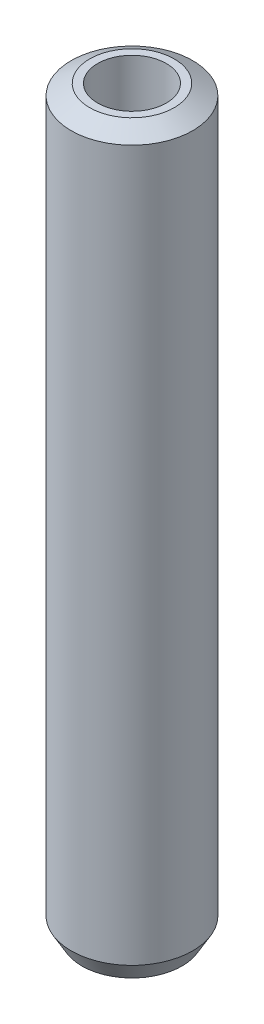
SolidWorks part; units mm, degrees
ref_plane "Front Plane" through (0, 0, 0) normal (0, 0, 1) x (1, 0, 0)
ref_plane "Top Plane" through (0, 0, 0) normal (0, 1, 0) x (1, 0, 0)
ref_plane "Right Plane" through (0, 0, 0) normal (1, 0, 0) x (0, 0, -1)
sketch "Sketch1" plane through (0, 0, 0) normal (0, 1, 0) x (1, 0, 0)
  circle A0 centre (0, 0) radius 7.5
  dimension "SHAFT_OD" = 15
extrude "Boss-Extrude1" add sketch "Sketch1" along normal blind 91.2657
sketch "Sketch2" plane through (0, 0, 0) normal (0, 1, 0) x (1, 0, 0)
  circle A0 centre (0, 0) radius 4.2371
  dimension "BORE_D" = 8.4741
extrude "Cut-Extrude1" cut sketch "Sketch2" along normal through all
chamfer "Chamfer1" distance 1.3175 angle 60 2 edges at (0, 91.2657, 7.5) (0, 0, 7.5) first distance on face at (0, 91.2657, 7.5) first distance on face at (0, 0, 4.2371)
